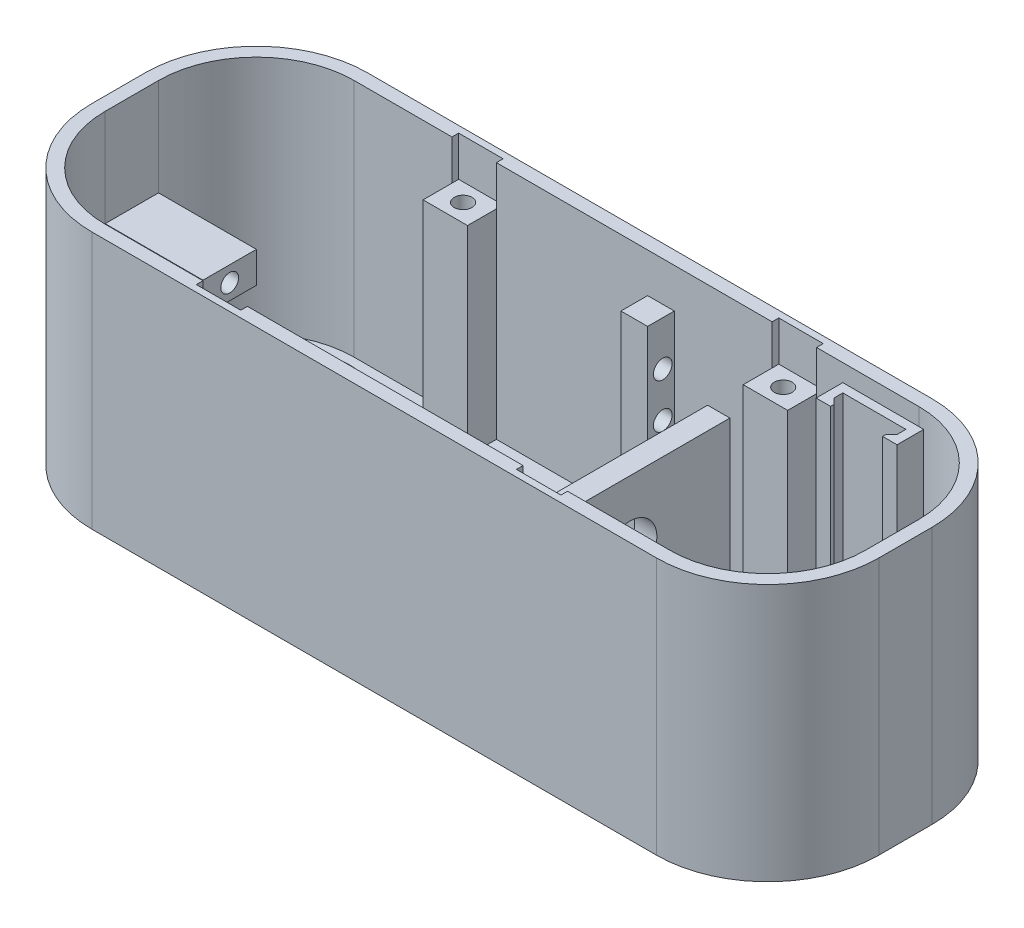
SolidWorks part; units mm, degrees
ref_plane "Front Plane" through (0, 0, 0) normal (0, 0, 1) x (1, 0, 0)
ref_plane "Top Plane" through (0, 0, 0) normal (0, 1, 0) x (1, 0, 0)
ref_plane "Right Plane" through (0, 0, 0) normal (1, 0, 0) x (0, 0, -1)
sketch "Sketch1" plane through (0, 0, 0) normal (0, 1, 0) x (1, 0, 0)
  line L1 (0, 0) -> (177, 0)
  line L2 (0, 0) -> (0, 62)
  line L3 (0, 62) -> (177, 62)
  line L4 (177, 0) -> (177, 62)
  dimension "D1" = 177
  dimension "D2" = 62
extrude "Boss-Extrude1" add sketch "Sketch1" along normal blind 60
sketch "Sketch2" plane through (0, 0, 0) normal (0, -1, 0) x (1, 0, 0)
  line L0 (0, -62) -> (0, 0) construction
  line L1 (0, 0) -> (177, 0) construction
  circle A0 centre (30, -31) radius 22
  dimension "D1" = 44
  dimension "D2" = 30
  dimension "D3" = 31
fillet "Fillet1" radius 25 4 edges at (177, 30, -62) (177, 30, 0) (0, 30, -62) (0, 30, 0)
sketch "Sketch3" plane through (0, 60, 0) normal (0, 1, 0) x (1, 0, 0)
  line L0 (177, 25) -> (177, 37) construction
  line L1 (152, 62) -> (25, 62) construction
  line L2 (138, 31) -> (157, 31)
  line L3 (138, 31) -> (138, 48)
  line L4 (138, 48) -> (157, 48)
  line L5 (157, 31) -> (157, 48)
  dimension "D1" = 17
  dimension "D2" = 19
  dimension "D3" = 20
  dimension "D4" = 14
extrude "Cut-Extrude1" cut sketch "Sketch3" against normal blind 70
ref_plane "Plane1" through (0, 57, 0) normal (0, 1, 0) x (1, 0, 0)
sketch "Sketch9" plane through (0, 57, 0) normal (0, 1, 0) x (1, 0, 0)
  line L0 (25, 59) -> (152, 59)
  line L1 (25, 3) -> (152, 3)
  line L2 (174, 25) -> (174, 37)
  line L3 (3, 37) -> (3, 25)
  line L6 (177, 25) -> (177, 37) construction
  arc A0 (25, 59) -> (3, 37) centre (25, 37) ccw
  arc A1 (25, 3) -> (3, 25) centre (25, 25) cw
  arc A2 (152, 59) -> (174, 37) centre (152, 37) cw
  arc A3 (152, 3) -> (174, 25) centre (152, 25) ccw
  point P26 (177, 31)
  dimension "D1" = 3
extrude "Cut-Extrude5" cut sketch "Sketch9" against normal blind 54
extrude "Boss-Extrude4" add sketch "Sketch2" against normal blind 7
sketch "Sketch11" plane through (0, 0, 0) normal (0, -1, 0) x (1, 0, 0)
  line L0 (0, -37) -> (0, -25) construction
  line L1 (25, 0) -> (152, 0) construction
  circle A0 centre (31, -31) radius 20
  dimension "D1" = 40
  dimension "D2" = 31
  dimension "D3" = 31
sketch "Sketch14" plane through (0, 0, 0) normal (0, -1, 0) x (1, 0, 0)
  line L0 (136.9, -55) -> (138.15, -53.75)
  line L2 (134.9, -53) -> (134.9, -55)
  line L4 (149.85, -53.75) -> (151.1, -55)
  line L6 (153.1, -55) -> (153.1, -53)
  line L8 (138.15, -53.75) -> (138.15, -53)
  line L9 (138.15, -53) -> (134.9, -53)
  line L10 (149.85, -53.75) -> (149.85, -53)
  line L11 (149.85, -53) -> (153.1, -53)
  line L12 (151.1, -55) -> (151.1, -57)
  line L13 (152, -62) -> (25, -62) construction
  line L14 (150.75, -62) -> (153.1, -62)
  line L15 (153.1, -55) -> (153.1, -62)
  line L16 (136.9, -55) -> (136.9, -57)
  line L17 (137.25, -62) -> (134.9, -62)
  line L18 (134.9, -62) -> (134.9, -55)
  line L19 (136.9, -57) -> (151.1, -57)
  line L20 (150.75, -62) -> (137.25, -62)
  line L21 (144, -62.6038) -> (144, -53.75) construction
  point P17 (144, -57)
  point P23 (144, -62)
  dimension "D1" = 135
  dimension "D2" = 2
  dimension "D3" = 14.2
  dimension "D4" = 2
  dimension "D5" = 0.75
  dimension "D6" = 7
  dimension "D7" = 5
extrude "Boss-Extrude6" add sketch "Sketch14" against normal blind 53
extrude "Cut-Extrude9" cut sketch "Sketch11" against normal blind 3.5
sketch "Sketch21" plane through (0, 60, 0) normal (0, 1, 0) x (1, 0, 0)
  line L0 (0, 37) -> (0, 25) construction
  circle A0 centre (31, 31) radius 25
  point P5 (0, 31)
  dimension "D1" = 50
  dimension "D2" = 31
extrude "Cut-Extrude10" cut sketch "Sketch21" against normal blind 18
sketch "Sketch23" plane through (0, 60, 0) normal (0, 1, 0) x (1, 0, 0)
  circle A0 centre (31, 31) radius 5
  dimension "D1" = 10
extrude "Cut-Extrude11" cut sketch "Sketch23" against normal blind 111
sketch "Sketch26" plane through (0, 0, 0) normal (0, -1, 0) x (1, 0, 0)
  line L0 (25, 0) -> (152, 0)
  line L1 (177, -25) -> (177, -37)
  line L2 (152, -62) -> (25, -62)
  line L3 (0, -25) -> (0, -37)
  line L4 (0, -37) -> (0, -25) construction
  line L6 (138, -48) -> (157, -48)
  line L7 (138, -48) -> (138, -31)
  line L8 (138, -31) -> (157, -31)
  line L9 (157, -48) -> (157, -31)
  arc A0 (0, -37) -> (25, -62) centre (25, -37) ccw construction
  arc A1 (25, 0) -> (0, -25) centre (25, -25) ccw
  arc A2 (0, -37) -> (25, -62) centre (25, -37) ccw
  arc A3 (152, -62) -> (177, -37) centre (152, -37) ccw
  arc A4 (177, -25) -> (152, 0) centre (152, -25) ccw
  circle A5 centre (31, -31) radius 20
  circle A6 centre (31, -31) radius 20 construction
  dimension "D1" = 19
  dimension "D2" = 17
  dimension "D3" = 14
extrude "Boss-Extrude23" add sketch "Sketch26" along normal blind 1
sketch "Sketch27" plane through (0, 0, 0) normal (-1, 0, 0) x (0, 0, 1)
  line L0 (-37, 60) -> (-25, 60) construction
  line L1 (-46, 20) -> (-16, 20)
  line L2 (-46, 20) -> (-46, 28)
  line L3 (-46, 28) -> (-16, 28)
  line L4 (-16, 20) -> (-16, 28)
  line L5 (-46, 20) -> (-16, 28) construction
  line L6 (-46, 28) -> (-16, 20) construction
  line L8 (-25, -1) -> (0, -1) construction
  point P0 (-31, 24)
  point P8 (-31, 60)
  dimension "D1" = 30
  dimension "D2" = 8
  dimension "D3" = 21
extrude "Cut-Extrude12" cut sketch "Sketch27" against normal blind 10
ref_plane "Plane2" through (0, 57, 0) normal (0, 1, 0) x (1, 0, 0)
sketch "Sketch30" plane through (0, 57, 0) normal (0, 1, 0) x (1, 0, 0)
  line L0 (0, 37) -> (0, 25) construction
  line L1 (25, 58) -> (152, 58)
  line L2 (4, 37) -> (4, 25)
  line L3 (25, 4) -> (152, 4)
  line L4 (173, 37) -> (173, 25)
  line L5 (177, 25) -> (177, 37) construction
  line L6 (25, 0) -> (152, 0) construction
  line L7 (152, 62) -> (25, 62) construction
  line L9 (-8.7918, 65.1377) -> (185.5455, 65.1377)
  line L10 (-8.7918, 65.1377) -> (-8.7918, -2.9849)
  line L11 (-8.7918, -2.9849) -> (185.5455, -2.9849)
  line L12 (185.5455, 65.1377) -> (185.5455, -2.9849)
  arc A0 (152, 58) -> (173, 37) centre (152, 37) cw
  arc A1 (152, 4) -> (173, 25) centre (152, 25) ccw
  arc A2 (4, 25) -> (25, 4) centre (25, 25) ccw
  arc A3 (25, 58) -> (4, 37) centre (25, 37) ccw
  point P8 (177, 31)
  dimension "D5" = 21
  dimension "D1" = 4
  dimension "D2" = 4
  dimension "D3" = 4
  dimension "D4" = 4
extrude "Cut-Extrude14" cut sketch "Sketch30" against normal blind 0.1
sketch "Sketch32" plane through (0, 60, 0) normal (0, 1, 0) x (1, 0, 0)
  circle A0 centre (52, 5.5) radius 2
  circle A1 centre (52, 56.5) radius 2
  circle A2 centre (164.5563, 10) radius 2
  circle A3 centre (124, 56.5) radius 2
  dimension "D1" = 4
extrude "Cut-Extrude15" cut sketch "Sketch32" against normal blind 20
sketch "Sketch35" plane through (0, 60, 0) normal (0, 1, 0) x (1, 0, 0)
  line L1 (-8.1358, 65.1129) -> (185.758, 65.1129)
  line L2 (-8.1358, 65.1129) -> (-8.1358, -3.735)
  line L3 (-8.1358, -3.735) -> (185.758, -3.735)
  line L4 (185.758, 65.1129) -> (185.758, -3.735)
extrude "Cut-Extrude16" cut sketch "Sketch35" against normal blind 3
sketch "Sketch38" plane through (0, 56.9, 0) normal (0, 1, 0) x (1, 0, 0)
  line L0 (52, 56.5) -> (52, 5.5) construction
  line L1 (52, 56.5) -> (124, 56.5) construction
  line L7 (47, 60.5) -> (57, 60.5)
  line L8 (47, 60.5) -> (47, 52.5)
  line L9 (47, 52.5) -> (57, 52.5)
  line L10 (57, 60.5) -> (57, 52.5)
  line L11 (47, 60.5) -> (57, 52.5) construction
  line L12 (47, 52.5) -> (57, 60.5) construction
  line L13 (119, 60.5) -> (129, 60.5)
  line L14 (119, 60.5) -> (119, 52.5)
  line L15 (119, 52.5) -> (129, 52.5)
  line L16 (129, 60.5) -> (129, 52.5)
  line L17 (119, 60.5) -> (129, 52.5) construction
  line L18 (119, 52.5) -> (129, 60.5) construction
  line L19 (47, 9.5) -> (57, 9.5)
  line L20 (47, 9.5) -> (47, 1.5)
  line L21 (47, 1.5) -> (57, 1.5)
  line L22 (57, 9.5) -> (57, 1.5)
  line L23 (47, 9.5) -> (57, 1.5) construction
  line L24 (47, 1.5) -> (57, 9.5) construction
  line L25 (119, 9.5) -> (129, 9.5)
  line L26 (119, 9.5) -> (119, 1.5)
  line L27 (119, 1.5) -> (129, 1.5)
  line L28 (129, 9.5) -> (129, 1.5)
  line L29 (119, 9.5) -> (129, 1.5) construction
  line L30 (119, 1.5) -> (129, 9.5) construction
  circle A0 centre (52, 56.5) radius 2
  circle A1 centre (124, 56.5) radius 2
  circle A2 centre (124, 5.5) radius 2
  circle A3 centre (52, 5.5) radius 2
  line M23 (25, 59) -> (152, 59)
  line M27 (152, 3) -> (25, 3)
  dimension "D9" = 4
  dimension "D1" = 8
  dimension "D3" = 8
  dimension "D4" = 10
  dimension "D6" = 8
  dimension "D7" = 8
extrude "Boss-Extrude26" add sketch "Sketch38" against normal up to surface (53.9 mm away) contours L22 L19 L20 A3 M27 | L22 L20 L21 M27 | L10 L7 L8 M23 | L10 L8 L9 A0 M23 | L16 L14 L15 A1 M23 | L16 L13 L14 M23 | L28 L25 L26 A2 M27 | L28 L26 L27 M27 region at (124, 56.9, -59.75) region at (124, 56.9, -58.8807) region at (52, 56.9, -59.75) region at (52, 56.9, -58.8807) region at (119.1193, 56.9, -6.25) region at (124, 56.9, -2.25) region at (52, 56.9, -9.3807) region at (52, 56.9, -2.25) up to face at (120.2018, 3, -44.7417)
sketch "Sketch39" plane through (0, 0, 0) normal (-1, 0, 0) x (0, 0, 1)
  line L0 (-31, 16.5055) -> (-31, 31.5055) construction
  line L1 (-37, 56.9) -> (-37, 28) construction
  line L2 (-25, 28) -> (-25, 56.9) construction
  line L3 (-25, -1) -> (-25, 20) construction
  line L5 (-37, 35.011) -> (-25, 35.011)
  line L6 (-37, 35.011) -> (-37, 28)
  line L7 (-37, 28) -> (-25, 28)
  line L8 (-25, 35.011) -> (-25, 28)
  line L9 (-37, 35.011) -> (-25, 28) construction
  line L10 (-37, 28) -> (-25, 35.011) construction
  line L11 (-37, 13.011) -> (-25, 13.011)
  line L12 (-37, 13.011) -> (-37, 20)
  line L13 (-37, 20) -> (-25, 20)
  line L14 (-25, 13.011) -> (-25, 20)
  line L15 (-37, 13.011) -> (-25, 20) construction
  line L16 (-37, 20) -> (-25, 13.011) construction
  circle A0 centre (-31, 31.5055) radius 2
  circle A1 centre (-31, 16.5055) radius 2
  dimension "D2" = 4
  dimension "D1" = 15
extrude "Cut-Extrude17" cut sketch "Sketch39" against normal blind 20 contours A0 | A1 region at (0, 31.5055, -31) region at (0, 16.5055, -31)
extrude "Cut-Extrude22" cut sketch "Sketch38<4>" against normal blind 9
sketch "Sketch38<4>" plane through (0, 56.9, 0) normal (0, 1, 0) x (1, 0, 0) same geometry as "Sketch38"
extrude "Boss-Extrude27" add sketch "Sketch39<4>" against normal blind 25
sketch "Sketch39<4>" plane through (0, 0, 0) normal (-1, 0, 0) x (0, 0, 1) same geometry as "Sketch39"
sketch "Sketch40" plane through (0, 3, 0) normal (0, 1, 0) x (1, 0, 0)
  line L1 (119, 9.5) -> (124, 9.5)
  line L2 (119, 9.5) -> (119, 44.5)
  line L3 (119, 44.5) -> (124, 44.5)
  line L4 (124, 9.5) -> (124, 44.5)
  line L5 (129, 9.5) -> (119, 9.5) construction
  dimension "D1" = 5
  dimension "D2" = 35
extrude "Boss-Extrude28" add sketch "Sketch40" along normal up to surface (44.9 mm away) up to face at (124, 47.9, -3.5)
sketch "Sketch41" plane through (119, 0, 0) normal (-1, 0, 0) x (0, 0, 1)
  line L0 (-3, 3) -> (-44.5, 3) construction
  line L1 (-3, 47.9) -> (-3, 3) construction
  circle A0 centre (-22, 33) radius 6.075
  dimension "D1" = 12.15
  dimension "D2" = 30
  dimension "D3" = 19
extrude "Cut-Extrude23" cut sketch "Sketch41" against normal up to next
sketch "Sketch43" plane through (0, 20, 0) normal (0, 1, 0) x (1, 0, 0)
  line L0 (0, 25) -> (0, 37)
  line L1 (1.6762, 46) -> (4.9251, 46)
  line L2 (3, 37) -> (3, 25)
  line L3 (4.9251, 16) -> (1.6762, 16)
  arc A0 (0, 37) -> (1.6762, 46) centre (25, 37) cw
  arc A1 (0, 25) -> (1.6762, 16) centre (25, 25) ccw
  arc A2 (3, 25) -> (4.9251, 16) centre (25, 25) ccw
  arc A3 (3, 37) -> (4.9251, 46) centre (25, 37) cw
extrude "Boss-Extrude29" add sketch "Sketch43" along normal up to next
sketch "Sketch44" plane through (0, 3, 0) normal (0, 1, 0) x (1, 0, 0)
  line L0 (97, 59) -> (97, 53)
  line L1 (57, 59) -> (119, 59) construction
  line L2 (97, 53) -> (91, 53)
  line L3 (91, 53) -> (91, 59)
  line L4 (91, 59) -> (97, 59)
  line L5 (97, 3) -> (97, 11)
  line L6 (119, 3) -> (57, 3) construction
  line L7 (97, 11) -> (91, 11)
  line L8 (91, 11) -> (91, 3)
  line L9 (91, 3) -> (97, 3)
  line L10 (119, 59) -> (119, 52.5) construction
  dimension "D1" = 22
  dimension "D2" = 6
  dimension "D3" = 6
  dimension "D4" = 8
extrude "Boss-Extrude30" add sketch "Sketch44" along normal blind 45
sketch "Sketch45" plane through (97, 0, 0) normal (1, 0, 0) x (0, 0, -1)
  circle A0 centre (7.6, 38) radius 2.1
  circle A1 centre (7.6, 28) radius 2.1
  circle A2 centre (56.4, 38) radius 2.1
  circle A3 centre (56.4, 28) radius 2.1
  dimension "D1" = 4.2
extrude "Cut-Extrude24" cut sketch "Sketch45" against normal blind 15
sketch "Sketch46" plane through (0, 0, 0) normal (-1, 0, 0) x (0, 0, 1)
  line L0 (-31, 31.5055) -> (-31, 16.5055) construction
  line L1 (-41, 27.5055) -> (-21, 27.5055)
  line L2 (-21, 27.5055) -> (-21, 20.5055)
  line L3 (-21, 20.5055) -> (-41, 20.5055)
  line L4 (-41, 20.5055) -> (-41, 27.5055)
  point P8 (-31, 27.5055)
  point P9 (-41, 24.0055)
  point P10 (-31, 24.0055)
  dimension "D1" = 20
  dimension "D2" = 7
extrude "Cut-Extrude25" cut sketch "Sketch46" against normal blind 10
sketch "Sketch47" plane through (0, 3, 0) normal (0, 1, 0) x (1, 0, 0)
  line L0 (174, 37) -> (174, 25) construction
  line L1 (99, 41) -> (109, 41)
  line L2 (99, 41) -> (99, 21)
  line L3 (99, 21) -> (109, 21)
  line L4 (109, 41) -> (109, 21)
  line L5 (174, 31) -> (133.8059, 31) construction
  line L6 (119, 59) -> (119, 52.5) construction
  point P8 (99, 31)
  dimension "D1" = 20
  dimension "D2" = 10
  dimension "D3" = 10
extrude "Cut-Extrude26" cut sketch "Sketch47" against normal blind 10
sketch "Sketch48" plane through (0, 3, 0) normal (0, 1, 0) x (1, 0, 0)
  line L1 (157, 31) -> (138, 31) construction
  point P0 (147.5, 31)
  point P1 (0, 0)
  point P4 (0, 0)
  point P6 (147.5, 31)
  point P7 (147.5, 31)
ref_point "Point2"
